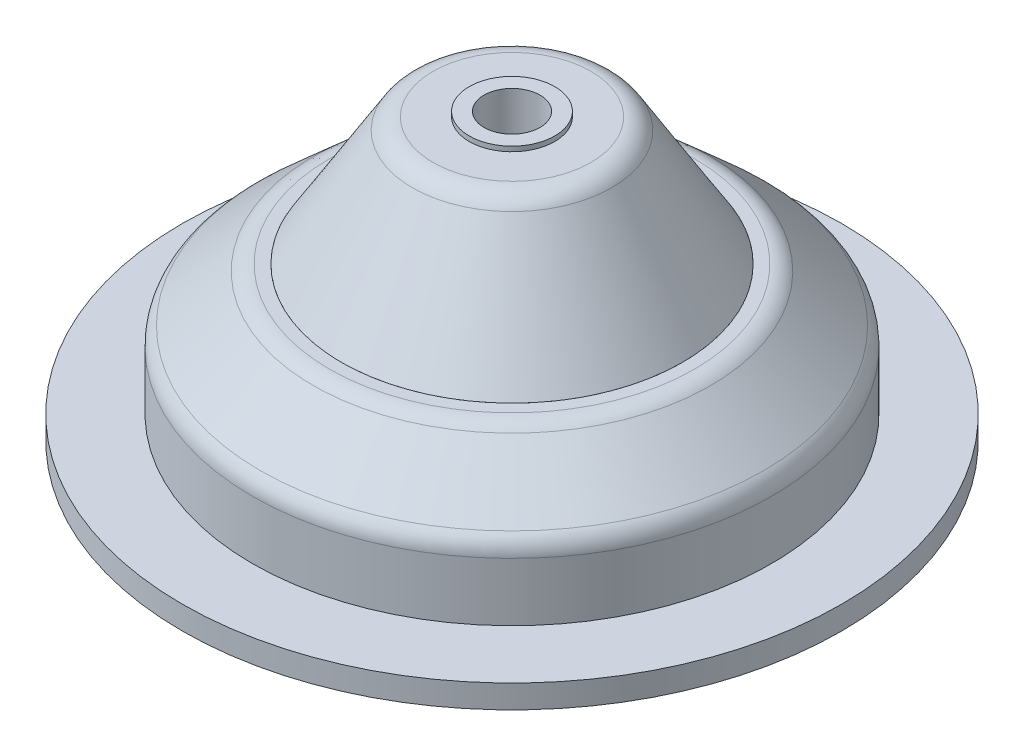
SolidWorks part; units mm, degrees
ref_plane "Front Plane" through (0, 0, 0) normal (0, 0, 1) x (1, 0, 0)
ref_plane "Top Plane" through (0, 0, 0) normal (0, 1, 0) x (1, 0, 0)
ref_plane "Right Plane" through (0, 0, 0) normal (1, 0, 0) x (0, 0, -1)
sketch "Sketch1" plane through (0, 0, 0) normal (0, 0, 1) x (1, 0, 0)
  line L0 (-34.5186, 0) -> (34.5186, 0) construction
  line L1 (-27.1716, 0) -> (27.1716, 0) construction
  line L2 (34.5186, 0) -> (27.1716, 0)
  line L3 (34.5186, 0) -> (34.5186, 2.4384)
  line L4 (34.5186, 2.4384) -> (27.1716, 2.4384)
  line L5 (34.5186, 0) -> (24.9555, 0)
  line L6 (27.1716, 2.4384) -> (27.1716, 8.5408)
  line L7 (24.9555, 0) -> (24.9555, 9.6774)
  line L8 (0, 0) -> (0, 35.1322) construction
  line L9 (14.7314, 0) -> (14.7314, 16.0274) construction
  line L10 (-20.066, 16.0274) -> (20.066, 16.0274) construction
  line L11 (20.789, 15.3813) -> (26.3242, 10.4348)
  line L12 (24.9555, 9.6774) -> (17.8498, 16.0274)
  line L13 (24.9555, 9.6774) -> (27.1716, 9.6774) construction
  line L14 (17.8498, 16.0274) -> (20.066, 16.0274) construction
  line L15 (17.8498, 16.0274) -> (19.0964, 16.0274)
  line L16 (0, 0) -> (0, 29.3878) construction
  line L17 (0, 16.0274) -> (0, 29.3624) construction
  line L18 (8.2671, 29.3624) -> (-8.2671, 29.3624)
  line L19 (17.8498, 16.0274) -> (10.4337, 28.1481)
  line L20 (2.9337, 29.3624) -> (-2.9337, 29.3624)
  line L21 (2.9337, 29.3624) -> (2.9337, 16.0274)
  line L22 (2.9337, 16.0274) -> (17.8498, 16.0274)
  arc A0 (27.1716, 8.5408) -> (26.3242, 10.4348) centre (24.6316, 8.5408) ccw
  arc A1 (19.0964, 16.0274) -> (20.789, 15.3813) centre (19.0964, 13.4874) cw
  arc A2 (8.2671, 29.3624) -> (10.4337, 28.1481) centre (8.2671, 26.8224) cw
  point P4 (0, 0)
  point P7 (0, 0)
  point P19 (0, 16.0274)
  point P29 (0, 29.3878)
  point P32 (0, 29.3624)
  point P36 (0, 29.3624)
  point P39 (9.6907, 29.3624)
  dimension "D9" = 2.54
  dimension "D10" = 2.54
  dimension "D16" = 2.54
  dimension "D1" = 69.0372
  dimension "D2" = 54.3433
  dimension "D3" = 2.4384
  dimension "D4" = 9.5631
  dimension "D5" = 9.6774
  dimension "D6" = 40.132
  dimension "D7" = 16.0274
  dimension "D8" = 14.7314
  dimension "D11" = 29.3878
  dimension "D12" = 29.3624
  dimension "D13" = 17.9578
  dimension "D14" = 5.8674
  dimension "D15" = 13.335
revolve "Revolve1" add sketch "Sketch1" angle 360 about L8 region at (26.7441, 5.7021, 0)
revolve "Revolve2" add sketch "Sketch1<3>" angle 360 about L8 region at (8.6059, 21.8421, 0)
sketch "Sketch1<3>" plane through (0, 0, 0) normal (0, 0, 1) x (1, 0, 0) same geometry as "Sketch1"
sketch "Sketch2" plane through (0, 29.3624, 0) normal (0, 1, 0) x (1, 0, 0)
  circle A0 centre (0, 0) radius 2.9337
  circle A1 centre (0, 0) radius 4.4768
  dimension "D1" = 8.9535
  dimension "D2" = 5.8674
extrude "Boss-Extrude1" add sketch "Sketch2" along normal blind 0.508
sketch "Sketch3" plane through (0, 16.0274, 0) normal (0, -1, 0) x (1, 0, 0)
  circle A0 centre (0, 0) radius 6.9913
  circle A1 centre (0, 0) radius 2.9337
  dimension "D1" = 13.9827
  dimension "D2" = 5.8674
ref_plane "Plane1" through (0, 7.9375, 0) normal (0, -1, 0) x (-1, 0, 0)
extrude "Boss-Extrude2" add sketch "Sketch3" along normal up to surface (8.0899 mm away) contours A0 | A1 up to plane "Plane1"
sketch "Sketch4" plane through (0, 7.9375, 0) normal (0, -1, 0) x (1, 0, 0)
  circle A0 centre (0, 0) radius 6.0452
  circle A1 centre (0, 0) radius 2.9337
  dimension "D1" = 12.0904
  dimension "D2" = 5.8674
extrude "Boss-Extrude3" add sketch "Sketch4" along normal blind 1.016
sketch "Sketch5" plane through (0, 16.0274, 0) normal (0, -1, 0) x (1, 0, 0)
  line L0 (0, 6.9914) -> (0, 17.8498)
  line L1 (-0.7121, 6.955) -> (-1.5102, 17.7858)
  line L2 (0.7937, 6.9461) -> (1.3025, 17.8023)
  line L3 (5.6672, 4.0942) -> (14.6479, 10.2008)
  line L4 (6.4124, 2.7857) -> (16.0685, 7.7731)
  line L5 (6.3792, -2.8608) -> (16.1581, -7.585)
  line L6 (5.6187, -4.1605) -> (14.766, -10.0291)
  line L7 (0.7121, -6.955) -> (1.5102, -17.7858)
  line L8 (-0.7937, -6.9461) -> (-1.3025, -17.8023)
  line L9 (-5.6672, -4.0942) -> (-14.6479, -10.2008)
  line L10 (-6.4124, -2.7857) -> (-16.0685, -7.7731)
  line L11 (-6.3792, 2.8608) -> (-16.1581, 7.585)
  line L12 (-5.6187, 4.1605) -> (-14.766, 10.0291)
  circle A0 centre (0, 0) radius 6.9914 construction
  circle A1 centre (0, 0) radius 17.8498 construction
  circle A2 centre (0, 0) radius 17.8498 construction
  arc A3 (-1.5102, 17.7858) -> (1.3025, 17.8023) centre (0, 0) cw
  arc A4 (-0.7121, 6.955) -> (0.7937, 6.9461) centre (0, 0) cw
  arc A5 (14.6479, 10.2008) -> (16.0685, 7.7731) centre (0, 0) cw
  arc A6 (5.6672, 4.0942) -> (6.4124, 2.7857) centre (0, 0) cw
  arc A7 (16.1581, -7.585) -> (14.766, -10.0291) centre (0, 0) cw
  arc A8 (6.3792, -2.8608) -> (5.6187, -4.1605) centre (0, 0) cw
  arc A9 (1.5102, -17.7858) -> (-1.3025, -17.8023) centre (0, 0) cw
  arc A10 (0.7121, -6.955) -> (-0.7937, -6.9461) centre (0, 0) cw
  arc A11 (-14.6479, -10.2008) -> (-16.0685, -7.7731) centre (0, 0) cw
  arc A12 (-5.6672, -4.0942) -> (-6.4124, -2.7857) centre (0, 0) cw
  arc A13 (-16.1581, 7.585) -> (-14.766, 10.0291) centre (0, 0) cw
  arc A14 (-6.3792, 2.8608) -> (-5.6187, 4.1605) centre (0, 0) cw
  point P38 (0, 0)
  circle M4 centre (0, 0) radius 17.8498
  circle M5 centre (0, 0) radius 6.9914
  dimension "D1" = 6.9914
  dimension "D4" = 17.8499
  dimension "D2" = 10.8309
  dimension "D3" = 10.8561
  dimension "D5" = 2.8127
  dimension "D6" = 175.785
  dimension "D7" = 6
extrude "Boss-Extrude4" add sketch "Sketch5" along normal blind 7.62 contours L12 L11 M5 M4 | L10 L9 M5 M4 | L6 L5 M5 M4 | L4 L3 M5 M4 | L8 L7 M5 M4 | L2 A3 L1 A4 region at (-11.2357, 16.0274, 6.4421) region at (11.1969, 16.0274, 6.5094) region at (-11.1969, 16.0274, -6.5094) region at (11.2357, 16.0274, -6.4421) region at (0.0389, 16.0274, -12.9514)
